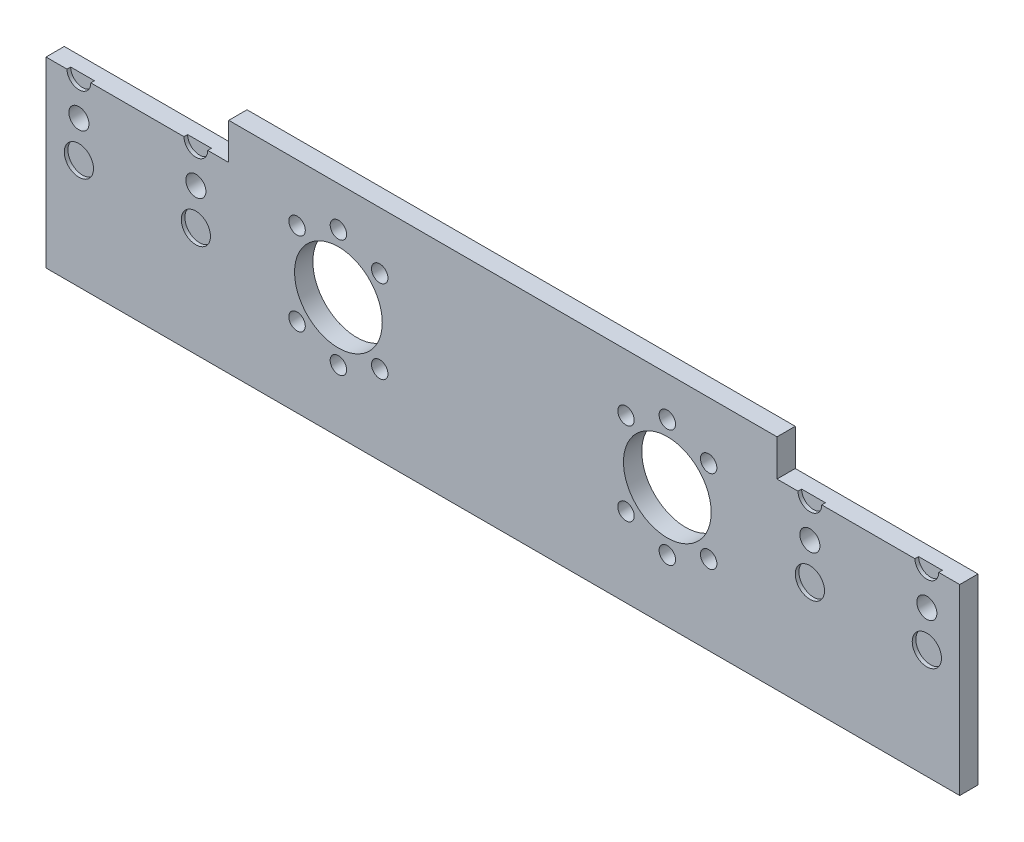
SolidWorks part; units mm, degrees
ref_plane "정면" through (0, 0, 0) normal (0, 0, 1) x (1, 0, 0)
ref_plane "윗면" through (0, 0, 0) normal (0, 1, 0) x (1, 0, 0)
ref_plane "우측면" through (0, 0, 0) normal (1, 0, 0) x (0, 0, -1)
sketch "스케치1" plane through (0, 0, 0) normal (0, 0, 1) x (1, 0, 0)
  line L1 (-145, 25) -> (145, 25)
  line L2 (-145, 25) -> (-145, -25)
  line L3 (-145, -25) -> (145, -25)
  line L4 (145, 25) -> (145, -25)
  line L5 (-145, 25) -> (145, -25) construction
  line L6 (-145, -25) -> (145, 25) construction
  point P0 (0, 0)
  dimension "D1" = 290
  dimension "D2" = 50
extrude "보스-돌출1" add sketch "스케치1" along normal blind 5
sketch "스케치3" plane through (0, 0, 5) normal (0, 0, 1) x (1, 0, 0)
  line L0 (-145, -25) -> (145, -25) construction
  line L1 (-145, 25) -> (-125, 25)
  line L2 (-145, 25) -> (-145, -25)
  line L3 (-145, -25) -> (-125, -25)
  line L4 (-125, 25) -> (-125, -25)
  dimension "D1" = 20
extrude "컷-돌출1" cut sketch "스케치3" against normal blind 10
mirror "대칭 복사1" about plane through (0, 0, 0) normal (1, 0, 0) of "컷-돌출1"
sketch "스케치4" plane through (0, 25, 0) normal (0, 1, 0) x (1, 0, 0)
  line L0 (125, 0) -> (-125, 0) construction
  line L1 (75, 0) -> (-75, 0)
  line L2 (75, 0) -> (75, -5)
  line L3 (75, -5) -> (-75, -5)
  line L4 (-75, 0) -> (-75, -5)
  line L5 (125, -5) -> (-125, -5) construction
  line L6 (-125, 0) -> (-125, -5) construction
  line L7 (125, 0) -> (125, -5) construction
  dimension "D1" = 50
  dimension "D2" = 50
extrude "보스-돌출2" add sketch "스케치4" along normal blind 10
sketch "스케치2" plane through (0, 0, 5) normal (0, 0, 1) x (1, 0, 0)
  line L2 (125, -25) -> (125, 25) construction
  line L3 (-125, -25) -> (125, -25) construction
  line L4 (9.7684, 8.045) -> (97.0125, 8.045) construction
  line L5 (44.999, 47.2348) -> (44.999, -36.4598) construction
  line L6 (0, -2.75) -> (0, 2.75) construction
  line L7 (-75, 35) -> (75, 35) construction
  circle A2 centre (56.308, -3.31) radius 2.25
  circle A3 centre (33.69, -3.31) radius 2.25
  circle A4 centre (44.999, -8) radius 2.25
  circle A5 centre (56.308, 19.4) radius 2.25
  circle A6 centre (44.999, 24.09) radius 2.25
  circle A7 centre (33.69, 19.4) radius 2.25
  circle A8 centre (-33.69, 19.4) radius 2.25
  circle A9 centre (-44.999, 24.09) radius 2.25
  circle A10 centre (-56.308, 19.4) radius 2.25
  circle A11 centre (-44.999, -8) radius 2.25
  circle A12 centre (-33.69, -3.31) radius 2.25
  circle A13 centre (-56.308, -3.31) radius 2.25
  circle A16 centre (44.999, 8.045) radius 12
  dimension "D4" = 68.692
  dimension "D5" = 15.6
  dimension "D7" = 4.5
  dimension "D11" = 4.5
  dimension "D2" = 24
  dimension "D3" = 91.31
  dimension "D8" = 21.69
  dimension "D10" = 17
extrude "컷-돌출2" cut sketch "스케치2" against normal blind 2.5
extrude "컷-돌출3" cut sketch "스케치2<2>" against normal through all contours A10 | A9 | A8 | A13 | A11 | A12 | A2 | A5 | A6 | A7 | A3 | A4 region at (56.308, -3.31, 5) region at (56.308, 19.4, 5) region at (44.999, 24.09, 5) region at (33.69, 19.4, 5) region at (-33.69, 19.4, 5) region at (-44.999, 24.09, 5) region at (-56.308, 19.4, 5) region at (-44.999, -8, 5) region at (-33.69, -3.31, 5) region at (-56.308, -3.31, 5)
sketch "스케치2<2>" plane through (0, 0, 5) normal (0, 0, 1) x (1, 0, 0) same geometry as "스케치2"
sketch "스케치5" plane through (0, 0, 5) normal (0, 0, 1) x (1, 0, 0)
  line L0 (-75, 25) -> (-125, 25) construction
  line L1 (-125, -25) -> (-125, 25) construction
  line L2 (0, -2.75) -> (0, 2.75) construction
  circle A0 centre (-84, 15) radius 2.75
  circle A1 centre (-116, 15) radius 2.75
  circle A2 centre (116, 15) radius 2.75
  circle A3 centre (84, 15) radius 2.75
  dimension "D3" = 5.5
  dimension "D4" = 5.5
  dimension "D5" = 9
  dimension "D1" = 10
  dimension "D2" = 10
  dimension "D6" = 41
extrude "컷-돌출4" cut sketch "스케치5" against normal through all
extrude "컷-돌출5" cut sketch "스케치2<3>" against normal blind 10 contours A16 region at (44.999, 8.045, 5)
sketch "스케치2<3>" plane through (0, 0, 5) normal (0, 0, 1) x (1, 0, 0) same geometry as "스케치2"
ref_plane "평면1" through (0, 0, 0) normal (1, 0, 0) x (0, 0, -1)
mirror "대칭 복사2" about plane through (0, 0, 0) normal (1, 0, 0) of "컷-돌출5"
sketch "스케치6" plane through (0, 0, 5) normal (0, 0, 1) x (1, 0, 0)
  line L0 (-75, 25) -> (-125, 25) construction
  line L1 (-125, -25) -> (-125, 25) construction
  line L2 (0, -2.75) -> (0, 2.75) construction
  circle A0 centre (-116, 25) radius 3.25
  circle A1 centre (-84, 25) radius 3.25
  circle A2 centre (84, 25) radius 3.25
  circle A3 centre (116, 25) radius 3.25
  circle A8 centre (-116, 5) radius 4
  circle A9 centre (-84, 5) radius 4
  circle A10 centre (84, 5) radius 4
  circle A11 centre (116, 5) radius 4
  dimension "D1" = 6.5
  dimension "D2" = 6.5
  dimension "D5" = 8
  dimension "D3" = 9
  dimension "D4" = 41
  dimension "D6" = 20
  dimension "D7" = 9
extrude "컷-돌출6" cut sketch "스케치6" against normal blind 1
